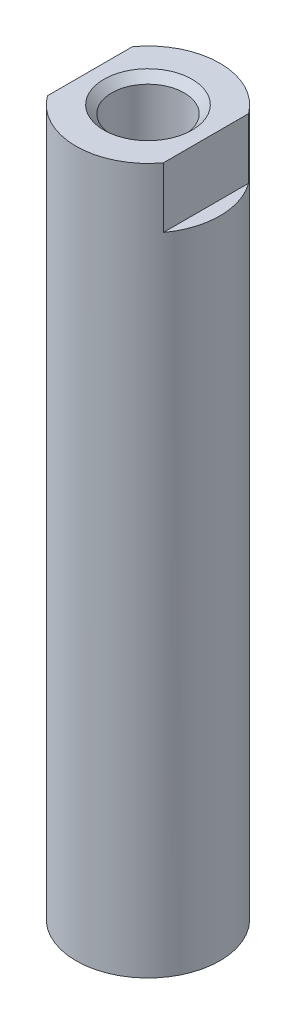
SolidWorks part; units mm, degrees
material "AISI 304"
ref_plane "Front Plane" through (0, 0, 0) normal (0, 0, 1) x (1, 0, 0)
ref_plane "Top Plane" through (0, 0, 0) normal (0, 1, 0) x (1, 0, 0)
ref_plane "Right Plane" through (0, 0, 0) normal (1, 0, 0) x (0, 0, -1)
sketch "Sketch1" plane through (0, 0, 0) normal (0, 0, 1) x (1, 0, 0)
  line L0 (0, 38.608) -> (3.937, 38.608)
  line L1 (3.937, 38.608) -> (3.937, 0)
  line L2 (3.937, 0) -> (0, 0)
  line L3 (0, 0) -> (0, 38.608)
  line L4 (0, 0) -> (0, 38.608) construction
revolve "Revolve1" add sketch "Sketch1" angle 360 about L4 reverse direction yes
ref_plane "Plane1" through (0, 38.608, 0) normal (0, 1, 0) x (1, 0, 0)
hole_wizard "Hole1" positions "Sketch3" profile "Sketch2" legacy
sketch "Sketch3" plane through (0, 38.608, 0) normal (0, 1, 0) x (1, 0, 0)
  point P0 (0, 0)
sketch "Sketch2" plane through (0, 38.608, 0) normal (1, 0, 0) x (0, 0, 1)
  line L0 (0, 0) -> (0, 11.684)
  line L1 (0, 11.684) -> (1.9837, 11.684)
  line L2 (1.9837, 11.684) -> (1.9837, 0.4293)
  line L3 (1.9837, 0.4293) -> (2.413, 0)
  line L4 (2.413, 0) -> (0, 0)
  line L5 (0, -6.4453) -> (0, 115.525) construction
  line L6 (-1.9837, 0.4293) -> (-2.413, 0) construction
  dimension "Diameter" = 3.9675
  dimension "Depth" = 11.684
  dimension "C-Sink Angle" = 90
  dimension "C-Sink Diameter" = 4.826
cosmetic thread "Cosmetic Thread1" parameters "D1"=11.684, "D2"=4.826
ref_plane "Plane2" through (0, 38.608, 0) normal (0, 1, 0) x (1, 0, 0)
ref_plane "Plane3" through (0, 38.608, 0) normal (0, 1, 0) x (1, 0, 0)
sketch "Sketch4" plane through (0, 38.608, 0) normal (0, 1, 0) x (1, 0, 0)
  line L0 (-6.35, 15.748) -> (-6.35, -15.748)
  line L1 (-6.35, -15.748) -> (6.35, -15.748)
  line L2 (6.35, -15.748) -> (6.35, 15.748)
  line L3 (6.35, 15.748) -> (-6.35, 15.748)
  line L4 (-3.175, 7.874) -> (-3.175, -7.874)
  line L5 (-3.175, -7.874) -> (3.175, -7.874)
  line L6 (3.175, -7.874) -> (3.175, 7.874)
  line L7 (3.175, 7.874) -> (-3.175, 7.874)
extrude "Cut-Extrude1" cut sketch "Sketch4" against normal blind 3.302
ref_plane "Plane4" through (0, 0, 0) normal (0, 1, 0) x (1, 0, 0)
ref_plane "b11 XY" through (0, 0, 0) normal (0, 1, 0) x (1, 0, 0)
ref_plane "b11 XZ" through (0, 0, 0) normal (0, 0, 1) x (1, 0, 0)
ref_plane "b11 YZ" through (0, 0, 0) normal (1, 0, 0) x (0, 0, -1)
ref_axis "b11 X" through (-80.9, 0, 0) along (1, 0, 0)
ref_axis "b11 Y" through (0, 0, 50) along (0, 0, -1)
ref_axis "b11 Z" through (0, 50, 0) along (0, -1, 0)
sketch3d "b11"
  point P0 (0, 0, 0)
ref_plane "b2 XY" through (0, 38.608, 0) normal (0, 1, 0) x (1, 0, 0)
ref_plane "b2 XZ" through (0, 0, 0) normal (0, 0, 1) x (1, 0, 0)
ref_plane "b2 YZ" through (0, 0, 0) normal (1, 0, 0) x (0, 0, -1)
ref_axis "b2 X" through (-80.9, 38.608, 0) along (1, 0, 0)
ref_axis "b2 Y" through (0, 38.608, 50) along (0, 0, -1)
ref_axis "b2 Z" through (0, 50, 0) along (0, -1, 0)
sketch3d "b2"
  point P0 (0, 38.608, 0)
ref_plane "e1 XY" through (0, 0, 0) normal (1, 0, 0) x (0, 0, -1)
ref_plane "e1 XZ" through (0, 38.608, 0) normal (0, -1, 0) x (-1, 0, 0)
ref_plane "e1 YZ" through (0, 0, -2.413) normal (0, 0, -1) x (-1, 0, 0)
ref_axis "e1 X" through (0, 38.608, 80.9) along (0, 0, -1)
ref_axis "e1 Y" through (0, -50, -2.413) along (0, 1, 0)
ref_axis "e1 Z" through (80.9, 38.608, -2.413) along (-1, 0, 0)
sketch3d "e1"
  point P0 (0, 38.608, -2.413)
ref_plane "e2 XY" through (0, 0, 0) normal (1, 0, 0) x (0, 0, -1)
ref_plane "e2 XZ" through (0, 38.608, 0) normal (0, -1, 0) x (-1, 0, 0)
ref_plane "e2 YZ" through (0, 0, 2.413) normal (0, 0, -1) x (-1, 0, 0)
ref_axis "e2 X" through (0, 38.608, 80.9) along (0, 0, -1)
ref_axis "e2 Y" through (0, -50, 2.413) along (0, 1, 0)
ref_axis "e2 Z" through (80.9, 38.608, 2.413) along (-1, 0, 0)
sketch3d "e2"
  point P0 (0, 38.608, 2.413)
ref_plane "f1 XY" through (0, 0, 0) normal (1, 0, 0) x (0, 0, -1)
ref_plane "f1 XZ" through (0, 38.608, 0) normal (0, -1, 0) x (-1, 0, 0)
ref_plane "f1 YZ" through (0, 0, 3.937) normal (0, 0, -1) x (-1, 0, 0)
ref_axis "f1 X" through (0, 38.608, 80.9) along (0, 0, -1)
ref_axis "f1 Y" through (0, -50, 3.937) along (0, 1, 0)
ref_axis "f1 Z" through (80.9, 38.608, 3.937) along (-1, 0, 0)
sketch3d "f1"
  point P0 (0, 38.608, 3.937)
ref_plane "f2 XY" through (0, 0, 0) normal (1, 0, 0) x (0, 0, -1)
ref_plane "f2 XZ" through (0, 38.608, 0) normal (0, -1, 0) x (-1, 0, 0)
ref_plane "f2 YZ" through (0, 0, -3.937) normal (0, 0, -1) x (-1, 0, 0)
ref_axis "f2 X" through (0, 38.608, 80.9) along (0, 0, -1)
ref_axis "f2 Y" through (0, -50, -3.937) along (0, 1, 0)
ref_axis "f2 Z" through (80.9, 38.608, -3.937) along (-1, 0, 0)
sketch3d "f2"
  point P0 (0, 38.608, -3.937)
ref_plane "h1 XY" through (0, 38.608, 0) normal (0, 1, 0) x (1, 0, 0)
ref_plane "h1 XZ" through (0, 0, 0) normal (0, 0, 1) x (1, 0, 0)
ref_plane "h1 YZ" through (-3.175, 0, 0) normal (1, 0, 0) x (0, 0, -1)
ref_axis "h1 X" through (-80.9, 38.608, 0) along (1, 0, 0)
ref_axis "h1 Y" through (-3.175, 38.608, 50) along (0, 0, -1)
ref_axis "h1 Z" through (-3.175, 50, 0) along (0, -1, 0)
sketch3d "h1"
  point P0 (-3.175, 38.608, 0)
ref_plane "h2 XY" through (0, 38.608, 0) normal (0, 1, 0) x (1, 0, 0)
ref_plane "h2 XZ" through (0, 0, 0) normal (0, 0, 1) x (1, 0, 0)
ref_plane "h2 YZ" through (3.175, 0, 0) normal (1, 0, 0) x (0, 0, -1)
ref_axis "h2 X" through (-80.9, 38.608, 0) along (1, 0, 0)
ref_axis "h2 Y" through (3.175, 38.608, 50) along (0, 0, -1)
ref_axis "h2 Z" through (3.175, 50, 0) along (0, -1, 0)
sketch3d "h2"
  point P0 (3.175, 38.608, 0)
ref_plane "rod XY" through (0, 38.608, 0) normal (0, 1, 0) x (1, 0, 0)
ref_plane "rod XZ" through (0, 0, 0) normal (0, 0, 1) x (1, 0, 0)
ref_plane "rod YZ" through (0, 0, 0) normal (1, 0, 0) x (0, 0, -1)
ref_axis "rod X" through (-80.9, 38.608, 0) along (1, 0, 0)
ref_axis "rod Y" through (0, 38.608, 50) along (0, 0, -1)
ref_axis "rod Z" through (0, 50, 0) along (0, -1, 0)
sketch3d "rod"
  point P0 (0, 38.608, 0)
ref_plane "rod to part XY" through (0, 0, 0) normal (0, 1, 0) x (1, 0, 0)
ref_plane "rod to part XZ" through (0, 0, 0) normal (0, 0, 1) x (1, 0, 0)
ref_plane "rod to part YZ" through (0, 0, 0) normal (1, 0, 0) x (0, 0, -1)
ref_axis "rod to part X" through (-80.9, 0, 0) along (1, 0, 0)
ref_axis "rod to part Y" through (0, 0, 50) along (0, 0, -1)
ref_axis "rod to part Z" through (0, 50, 0) along (0, -1, 0)
sketch3d "rod to part"
  point P0 (0, 0, 0)
ref_plane "to rod pivot XY" through (0, 38.608, 0) normal (0, 1, 0) x (1, 0, 0)
ref_plane "to rod pivot XZ" through (0, 0, 0) normal (0, 0, 1) x (1, 0, 0)
ref_plane "to rod pivot YZ" through (0, 0, 0) normal (1, 0, 0) x (0, 0, -1)
ref_axis "to rod pivot X" through (-80.9, 38.608, 0) along (1, 0, 0)
ref_axis "to rod pivot Y" through (0, 38.608, 50) along (0, 0, -1)
ref_axis "to rod pivot Z" through (0, 50, 0) along (0, -1, 0)
sketch3d "to rod pivot"
  point P0 (0, 38.608, 0)
ref_plane "to rod pivot1 XY" through (0, 0, 0) normal (0, 1, 0) x (1, 0, 0)
ref_plane "to rod pivot1 XZ" through (0, 0, 0) normal (0, 0, 1) x (1, 0, 0)
ref_plane "to rod pivot1 YZ" through (0, 0, 0) normal (1, 0, 0) x (0, 0, -1)
ref_axis "to rod pivot1 X" through (-80.9, 0, 0) along (1, 0, 0)
ref_axis "to rod pivot1 Y" through (0, 0, 50) along (0, 0, -1)
ref_axis "to rod pivot1 Z" through (0, 50, 0) along (0, -1, 0)
sketch3d "to rod pivot1"
  point P0 (0, 0, 0)
